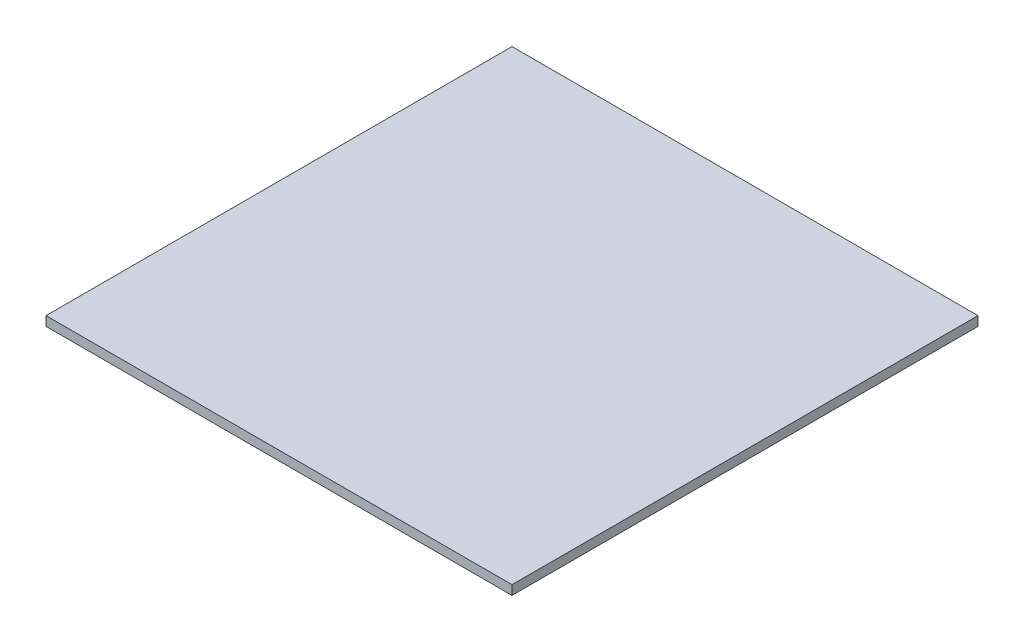
SolidWorks part; units mm, degrees
ref_plane "Alzado" through (0, 0, 0) normal (0, 0, 1) x (1, 0, 0)
ref_plane "Planta" through (0, 0, 0) normal (0, 1, 0) x (1, 0, 0)
ref_plane "Vista lateral" through (0, 0, 0) normal (1, 0, 0) x (0, 0, -1)
sketch "Croquis1" plane through (0, 0, 0) normal (0, 1, 0) x (1, 0, 0)
  line L1 (-100, 100) -> (100, 100)
  line L2 (-100, 100) -> (-100, -100)
  line L3 (-100, -100) -> (100, -100)
  line L4 (100, 100) -> (100, -100)
  line L5 (-100, 100) -> (100, -100) construction
  line L6 (-100, -100) -> (100, 100) construction
  point P0 (0, 0)
  dimension "D1" = 200
  dimension "D2" = 200
extrude "Saliente-Extruir1" add sketch "Croquis1" along normal blind 4
